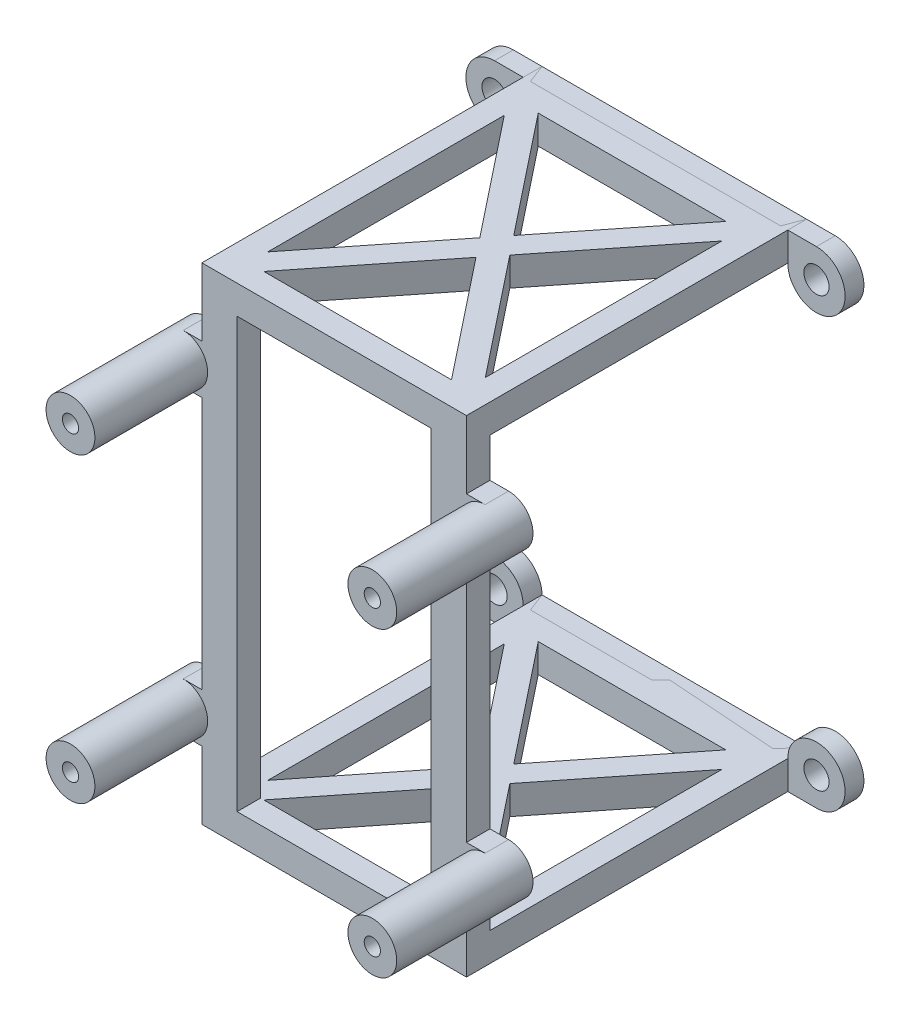
SolidWorks part; units mm, degrees
material "ABS PC"
ref_plane "Front Plane" through (0, 0, 0) normal (0, 0, 1) x (1, 0, 0)
ref_plane "Top Plane" through (0, 0, 0) normal (0, 1, 0) x (1, 0, 0)
ref_plane "Right Plane" through (0, 0, 0) normal (1, 0, 0) x (0, 0, -1)
sketch "Sketch1" plane through (0, 0, 0) normal (0, 0, 1) x (1, 0, 0)
  line L0 (-21.7551, 32.8676) -> (21.7551, 32.8676)
  line L1 (-21.7551, -28.9941) -> (21.7551, -28.9941) construction
  line L2 (-21.7551, -28.9941) -> (-21.7551, 28.9941) construction
  line L3 (-21.7551, 28.9941) -> (21.7551, 28.9941) construction
  line L4 (21.7551, -28.9941) -> (21.7551, 28.9941) construction
  line L5 (-21.7551, -28.9941) -> (21.7551, 28.9941) construction
  line L6 (-21.7551, 28.9941) -> (21.7551, -28.9941) construction
  line L7 (-21.7551, -32.8676) -> (21.7551, -32.8676)
  line L8 (-17.8816, 28.9941) -> (17.8816, 28.9941)
  line L9 (-17.8816, -28.9941) -> (17.8816, -28.9941)
  line L15 (-19.4303, -25.8958) -> (19.4303, 25.8958) construction
  line L16 (-19.4303, 25.8958) -> (19.4303, -25.8958) construction
  circle A0 centre (-21.7551, 28.9941) radius 3.8735
  circle A1 centre (21.7551, 28.9941) radius 3.8735
  circle A2 centre (21.7551, 28.9941) radius 1.7018
  circle A3 centre (-21.7551, 28.9941) radius 1.7018
  circle A4 centre (-21.7551, -28.9941) radius 3.8735
  circle A5 centre (-21.7551, -28.9941) radius 1.7018
  circle A6 centre (21.7551, -28.9941) radius 1.7018
  circle A7 centre (21.7551, -28.9941) radius 3.8735
  point P0 (0, 0)
  point P22 (0, 0)
  dimension "D3" = 7.747
  dimension "D4" = 3.4036
  dimension "D1" = 43.5102
  dimension "D2" = 57.9882
extrude "Boss-Extrude2" add sketch "Sketch1" along normal blind 2.54 contours A4 A0 | A0 A3 | A1 L0 A0 | A1 A2 | A7 A1 | A7 A6 | A7 A4 L7 | A4 A5 region at (0, 30.9784, 0) region at (-19.0936, 31.6556, 0) region at (24.4166, 31.6556, 0) region at (0, -30.9784, 0) region at (-24.4166, -26.3326, 0) region at (19.0936, -31.6556, 0)
sketch "Sketch2" plane through (0, 0, 2.54) normal (0, 0, 1) x (1, 0, 0)
  line L4 (-17.8816, 28.9941) -> (17.8816, 28.9941)
  line L9 (-17.8816, -28.9941) -> (17.8816, -28.9941)
  line L10 (17.8816, -28.9941) -> (17.8816, -32.8676)
  line L11 (17.8816, 28.9941) -> (17.8816, 32.8676)
  line L12 (-21.7551, 32.8676) -> (21.7551, 32.8676) construction
  line L13 (17.8816, 32.8676) -> (-17.8816, 32.8676)
  line L14 (-17.8816, 32.8676) -> (-17.8816, 28.9941)
  line L15 (-21.7551, -32.8676) -> (21.7551, -32.8676) construction
  line L16 (17.8816, -32.8676) -> (-17.8816, -32.8676)
  line L17 (-17.8816, -32.8676) -> (-17.8816, -28.9941)
  point P4 (0, 0)
extrude "Boss-Extrude3" add sketch "Sketch2" along normal blind 45.974 from surface separate body starting at face at (0, -28.593, 0)
sketch "Sketch6" plane through (0, 32.8676, 0) normal (0, 1, 0) x (1, 0, 0)
  line L0 (-17.8816, -2.54) -> (17.8816, -2.54)
  line L1 (-21.7551, -2.54) -> (21.7551, -2.54) construction
  line L2 (-12.6804, -42.799) -> (14.7066, -8.2696)
  line L3 (-14.7066, -42.799) -> (14.7066, -42.799)
  line L4 (17.8816, 0) -> (-17.8816, 0)
  line L5 (-17.8816, 0) -> (-17.8816, -45.974)
  line L6 (-17.8816, -45.974) -> (17.8816, -45.974)
  line L7 (17.8816, -45.974) -> (17.8816, 0)
  line L9 (-17.8816, -2.54) -> (-17.8816, -45.974)
  line L10 (-17.8816, -45.974) -> (17.8816, -45.974)
  line L11 (17.8816, -45.974) -> (17.8816, -2.54)
  line L12 (-14.7066, -42.799) -> (-14.7066, -5.715)
  line L13 (-14.7066, -5.715) -> (14.7066, -5.715)
  line L14 (14.7066, -42.799) -> (14.7066, -5.715)
  line L15 (-14.7066, -42.799) -> (14.7066, -5.715) construction
  line L16 (-14.7066, -5.715) -> (14.7066, -42.799) construction
  line L17 (12.6804, -5.715) -> (-14.7066, -40.2444)
  line L18 (12.6804, -42.799) -> (-14.7066, -8.2696)
  line L19 (-12.6804, -5.715) -> (14.7066, -40.2444)
  point P8 (0, -24.257)
  dimension "D2" = 3.175
  dimension "D3" = 3.175
  dimension "D4" = 3.175
  dimension "D5" = 3.175
  dimension "D6" = 1.5875
  dimension "D7" = 1.5875
  dimension "D8" = 1.5875
  dimension "D9" = 1.5875
  dimension "D1" = 0
extrude "Cut-Extrude3" cut sketch "Sketch6" against normal through all contours L17 L18 L12 | L13 L19 L17 | L2 L19 L14 | L3 L18 L2 region at (0, 32.8676, 37.4699) region at (10.4798, 32.8676, 24.257) region at (-10.4798, 32.8676, 24.257) region at (0, 32.8676, 11.0441)
sketch "Sketch7" plane through (0, 0, 0) normal (0, 0, 1) x (1, 0, 0)
  line L0 (-13.1191, -17.1002) -> (-13.1191, 17.1002)
  line L1 (-20.4, -20.4) -> (20.4, -20.4) construction
  line L2 (-20.4, -20.4) -> (-20.4, 20.4) construction
  line L3 (-20.4, 20.4) -> (20.4, 20.4) construction
  line L4 (20.4, -20.4) -> (20.4, 20.4) construction
  line L5 (-20.4, -20.4) -> (20.4, 20.4) construction
  line L6 (-20.4, 20.4) -> (20.4, -20.4) construction
  line L7 (-17.8816, 32.8676) -> (-17.8816, 23.6999)
  line L8 (-20.4, 23.6999) -> (-17.8816, 23.6999)
  line L9 (-13.1191, 32.8676) -> (-13.1191, 17.1002)
  line L10 (-20.4, 17.1002) -> (-17.8816, 17.1002)
  line L11 (13.1191, 32.8676) -> (13.1191, 17.1002)
  line L12 (17.8816, 17.1002) -> (20.4, 17.1002)
  line L13 (20.4, 23.6999) -> (17.8816, 23.6999)
  line L14 (17.8816, 32.8676) -> (17.8816, 23.6999)
  line L15 (-13.1191, -32.8676) -> (-13.1191, -17.1002)
  line L16 (-20.4, -17.1002) -> (-17.8816, -17.1002)
  line L17 (-20.4, -23.6999) -> (-17.8816, -23.6999)
  line L18 (-17.8816, -23.6999) -> (-17.8816, -32.8676)
  line L19 (-17.8816, -32.8676) -> (-13.1191, -32.8676)
  line L20 (-17.8816, 32.8676) -> (-13.1191, 32.8676)
  line L21 (13.1191, 32.8676) -> (17.8816, 32.8676)
  line L22 (20.4, -17.1002) -> (17.8816, -17.1002)
  line L23 (13.1191, -17.1002) -> (13.1191, -32.8676)
  line L24 (-17.8816, -32.8676) -> (17.8816, -32.8676) construction
  line L25 (13.1191, -32.8676) -> (17.8816, -32.8676)
  line L26 (17.8816, -32.8676) -> (17.8816, -23.6999)
  line L27 (17.8816, -23.6999) -> (20.4, -23.6999)
  line L28 (-17.8816, 17.1002) -> (-17.8816, -17.1002)
  line L29 (13.1191, 17.1002) -> (13.1191, -17.1002)
  line L30 (17.8816, 17.1002) -> (17.8816, -17.1002)
  circle A0 centre (20.4, 20.4) radius 3.2998
  circle A1 centre (-20.4, 20.4) radius 3.2998
  circle A2 centre (-20.4, -20.4) radius 3.2998
  circle A3 centre (20.4, -20.4) radius 3.2998
  circle A4 centre (-20.4, 20.4) radius 1.0999
  circle A5 centre (20.4, 20.4) radius 1.0999
  circle A6 centre (-20.4, -20.4) radius 1.0999
  circle A7 centre (20.4, -20.4) radius 1.0999
  point P0 (0, 0)
  dimension "D3" = 6.5997
  dimension "D8" = 2.1999
  dimension "D1" = 40.8
  dimension "D2" = 40.8
  dimension "D4" = 4.7625
  dimension "D5" = 4.7625
  dimension "D6" = 4.7625
  dimension "D7" = 4.7625
extrude "Boss-Extrude4" add sketch "Sketch7" against normal blind 3.175 from surface contours A1 L10 L9 L20 L7 L8 | A1 | A0 | A0 L13 L14 L21 L11 L12 | A3 L22 L23 L25 L26 L27 | A3 | A2 | A2 L17 L18 L19 L15 L16 region at (-15.5046, 0, 0) region at (-23.6065, -20.4, 0) region at (-18.1327, 22.6674, 0) region at (15.5046, 0, 0) region at (22.6674, 22.6674, 0) region at (17.1935, -20.4, 0) starting at face at (0, 30.9308, 45.974)
sketch "Sketch8" plane through (0, 0, 45.974) normal (0, 0, 1) x (1, 0, 0)
  circle A0 centre (-20.4, 20.4) radius 3.2998
  circle A1 centre (-20.4, 20.4) radius 1.0999
  circle A2 centre (20.4, 20.4) radius 1.0999
  circle A3 centre (20.4, 20.4) radius 3.2998
  circle A4 centre (20.4, -20.4) radius 1.0999
  circle A5 centre (20.4, -20.4) radius 3.2998
  circle A6 centre (-20.4, -20.4) radius 1.0999
  circle A7 centre (-20.4, -20.4) radius 3.2998
extrude "Boss-Extrude5" add sketch "Sketch8" along normal blind 15.24
